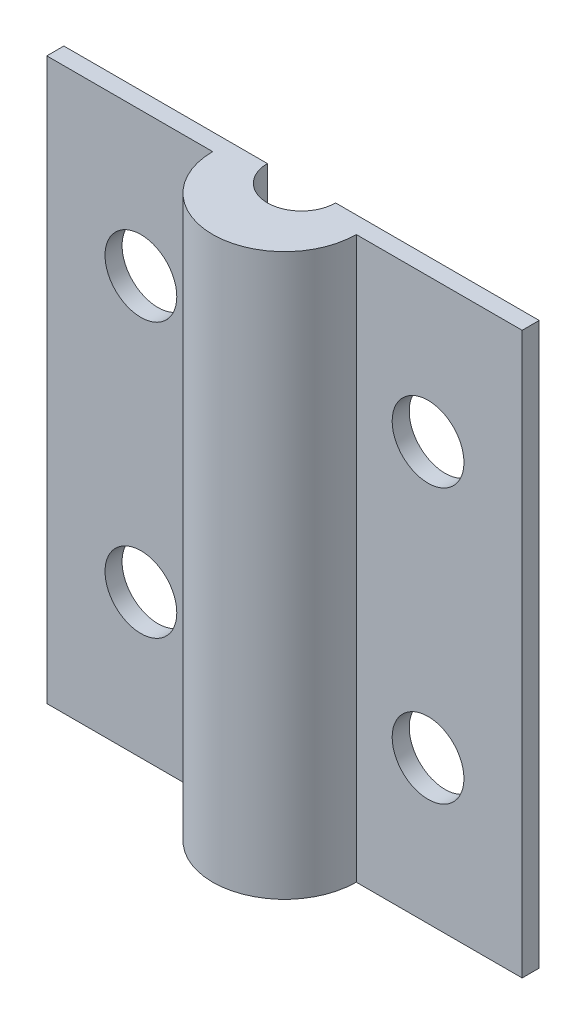
SolidWorks part; units mm, degrees
ref_plane "Front Plane" through (0, 0, 0) normal (0, 0, 1) x (1, 0, 0)
ref_plane "Top Plane" through (0, 0, 0) normal (0, 1, 0) x (1, 0, 0)
ref_plane "Right Plane" through (0, 0, 0) normal (1, 0, 0) x (0, 0, -1)
sketch "Sketch1" plane through (0, 0, 0) normal (0, 0, 1) x (1, 0, 0)
  line L1 (-41.3467, 25.8704) -> (-10.1219, 25.8704)
  line L2 (-41.3467, 25.8704) -> (-41.3467, 6.023)
  line L3 (-41.3467, 6.023) -> (-10.1219, 6.023)
  line L4 (-10.1219, 25.8704) -> (-10.1219, 6.023)
extrude "Boss-Extrude1" add sketch "Sketch1" along normal blind 3.302
sketch "Sketch2" plane through (0, 6.023, 0) normal (0, -1, 0) x (1, 0, 0)
  line L0 (-41.3467, 0) -> (-10.1219, 0) construction
  line L1 (-25.7343, 3.302) -> (-25.7343, 0) construction
  line L2 (-41.3467, 3.302) -> (-10.1219, 3.302) construction
  line L3 (-41.3467, 0) -> (-25.7343, 0) construction
  circle A0 centre (-25.7343, 0) radius 1.2065
  dimension "D1" = 2.413
  dimension "D2" = 3.302
  dimension "D3" = 15.6124
extrude "Cut-Extrude1" cut sketch "Sketch2" along direction (0, 1, 0) on the side against the normal up to surface (19.8473 mm away) up to face at (-25.7343, 25.8704, 1.651)
sketch "Sketch3" plane through (0, 6.023, 0) normal (0, -1, 0) x (1, 0, 0)
  line L0 (-41.3467, 3.302) -> (-10.1219, 3.302) construction
  line L1 (-34.5065, 3.302) -> (-28.2743, 3.302)
  line L2 (-34.5065, 3.302) -> (-34.5065, 0.6033)
  line L3 (-34.5065, 0.6033) -> (-28.2743, 0.6033)
  line L4 (-28.2743, 3.302) -> (-28.2743, 0.6033)
  line L5 (-31.3904, 0) -> (-31.3904, 0.6033) construction
  line L6 (-41.3467, 0) -> (-26.9408, 0) construction
  line L7 (-25.7343, 1.2065) -> (-28.2743, 1.2065) construction
  arc A0 (-24.5278, 0) -> (-26.9408, 0) centre (-25.7343, 0) ccw construction
  dimension "D1" = 2.6987
  dimension "D2" = 6.2321
  dimension "D3" = 2.54
extrude "Cut-Extrude2" cut sketch "Sketch3" against normal up to surface (19.8473 mm away) up to face at (-25.7343, 25.8704, 1.3018)
ref_plane "Plane1" through (-25.7343, 0, 0) normal (-1, 0, 0) x (0, 0, 1)
mirror "Mirror1" about plane through (-25.7343, 0, 0) normal (-1, 0, 0) of "Cut-Extrude2"
sketch "Sketch4" plane through (0, 6.023, 0) normal (0, -1, 0) x (1, 0, 0)
  line L0 (-25.7343, 4.1869) -> (-25.7343, -4.1869) construction
  line L1 (-25.7343, 0) -> (-25.7343, 0.6032) construction
  line L2 (-25.7343, 0.6032) -> (-23.1943, 0.6033) construction
  circle A1 centre (-25.7343, 0.6032) radius 2.54
  dimension "D1" = 5.08
  dimension "D2" = 2.54
sketch "Sketch5" plane through (0, 6.023, 0) normal (0, -1, 0) x (1, 0, 0)
  line L0 (-28.2743, 0.6033) -> (-28.2743, 3.302)
  line L1 (-28.2743, 3.302) -> (-23.1943, 3.302)
  line L2 (-23.1943, 3.302) -> (-23.1943, 0.6032)
  arc A0 (-28.2743, 0.6033) -> (-23.1943, 0.6032) centre (-25.7343, 0.6032) cw
extrude "Cut-Extrude4" cut sketch "Sketch5" against normal up to surface (19.8473 mm away) up to face at (-25.7343, 25.8704, 1.6737)
sketch "Sketch6" plane through (0, 6.023, 0) normal (0, -1, 0) x (1, 0, 0)
  line L0 (-41.3467, 0) -> (-26.9408, 0) construction
  line L5 (-41.3467, 3.302) -> (-34.1438, 3.302)
  line L6 (-41.3467, 3.302) -> (-41.3467, 0)
  line L7 (-41.3467, 0) -> (-34.1438, 0)
  line L8 (-34.1438, 3.302) -> (-34.1438, 0)
extrude "Cut-Extrude5" cut sketch "Sketch6" against normal up to surface (19.8473 mm away) up to face at (-25.7343, 25.8704, 1.614)
mirror "Mirror2" about plane through (-25.7343, 0, 0) normal (-1, 0, 0) of "Cut-Extrude5"
sketch "Sketch7" plane through (0, 0, 0.6033) normal (0, 0, 1) x (1, 0, 0)
  line L0 (-30.8143, 6.023) -> (-30.8143, 11.103) construction
  line L1 (-34.1438, 6.023) -> (-28.2743, 6.023) construction
  line L2 (-30.8143, 11.103) -> (-25.7343, 11.103) construction
  line L4 (-25.7343, 4.1869) -> (-25.7343, -4.1869) construction
  circle A0 centre (-30.8143, 11.103) radius 1.27
  dimension "D1" = 2.54
  dimension "D2" = 5.08
extrude "Cut-Extrude6" cut sketch "Sketch7" against normal up to surface (0.6032 mm away) up to face at (-30.5423, 15.9467, 0)
ref_axis "Axis1" through (-23.1943, 15.9467, 0.6033) along (1, 0, 0)
ref_axis "Axis2" through (-17.3249, 15.9467, 0.6033) along (0, 0, -1)
ref_plane "Plane2" through (0, 15.9467, 0) normal (0, -1, 0) x (-1, 0, 0)
mirror "Mirror3" about plane through (0, 15.9467, 0) normal (0, -1, 0) of "Cut-Extrude6"
mirror "Mirror4" about plane through (-25.7343, 0, 0) normal (-1, 0, 0) of "Mirror3"
